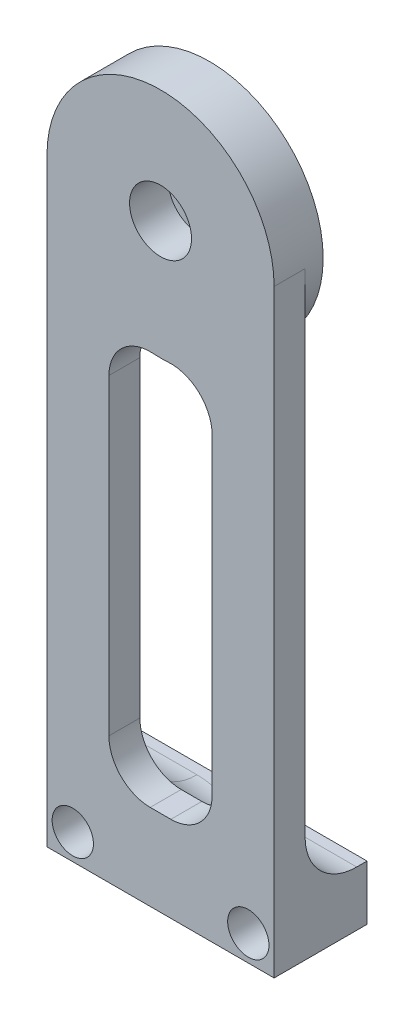
SolidWorks part; units mm, degrees
ref_plane "Front Plane" through (0, 0, 0) normal (0, 0, 1) x (1, 0, 0)
ref_plane "Top Plane" through (0, 0, 0) normal (0, 1, 0) x (1, 0, 0)
ref_plane "Right Plane" through (0, 0, 0) normal (1, 0, 0) x (0, 0, -1)
sketch "Sketch1" plane through (0, 0, 0) normal (0, 0, 1) x (1, 0, 0)
  line L0 (0, 29) -> (0, -29) construction
  line L1 (-11, 29) -> (-11, -29)
  line L2 (11, 29) -> (11, -29)
  line L3 (-11, -29) -> (11, -29)
  line L5 (-11, -29) -> (11, -29)
  line L6 (-11, -29) -> (-11, -23.69)
  line L7 (-11, -23.69) -> (11, -23.69)
  line L8 (11, -29) -> (11, -23.69)
  line L10 (-5, 18.6438) -> (-5, -20.69)
  line L11 (-5, -20.69) -> (5, -20.69)
  line L12 (5, 18.6438) -> (5, -20.69)
  circle A0 centre (0, 29) radius 11
  arc A2 (-5, 18.6438) -> (5, 18.6438) centre (0, 29) ccw
  point P8 (0, 0)
  dimension "D2" = 22
  dimension "D6" = 6
  dimension "D7" = 11.5
  dimension "D1" = 58
  dimension "D3" = 5.31
  dimension "D4" = 3
  dimension "D5" = 6
extrude "Boss-Extrude1" add sketch "Sketch1" along normal blind 3 contours A0 | L0 A0 L1 | A0 L0 L2 | L6 L5 L8 L7 region at (0, 17.9429, 0) region at (0, 29, 0)
extrude "Boss-Extrude2" add sketch "Sketch1<3>" against normal blind 1.75 contours A0 region at (0, 29, 0)
sketch "Sketch1<3>" plane through (0, 0, 0) normal (0, 0, 1) x (1, 0, 0) same geometry as "Sketch1"
sketch "Sketch2" plane through (0, 0, 3) normal (0, 0, 1) x (1, 0, 0)
  circle A0 centre (0, 29) radius 1.75
  circle A3 centre (0, 29) radius 3
  dimension "D1" = 3.5
  dimension "D2" = 6
extrude "Cut-Extrude1" cut sketch "Sketch2" against normal up to surface (4.75 mm away) contours A0 region at (0, 29, 3) up to face at (11, 29, -1.75)
extrude "Cut-Extrude2" cut sketch "Sketch2<3>" against normal offset from surface (3.75 mm away) 1 contours A3 A0 region at (-2.9151, 29, 3) up to face at (1.75, 29, -1.75)
sketch "Sketch2<3>" plane through (0, 0, 3) normal (0, 0, 1) x (1, 0, 0) same geometry as "Sketch2"
extrude "Boss-Extrude3" add sketch "Sketch1<6>" against normal blind 6 contours L7 L0 L5 L2 | L0 L7 L1 L3 region at (-5.5, -26.345, 0) region at (5.5, -26.345, 0)
sketch "Sketch1<6>" plane through (0, 0, 0) normal (0, 0, 1) x (1, 0, 0) same geometry as "Sketch1"
sketch "Sketch3" plane through (0, 0, 3) normal (0, 0, 1) x (1, 0, 0)
  line L1 (-8.5, -26.505) -> (8.5, -26.505) construction
  line L2 (-11, -29) -> (11, -29) construction
  circle A1 centre (-8.5, -26.505) radius 1.1
  circle A2 centre (8.5, -26.505) radius 1.1
  circle A3 centre (-8.5, -26.505) radius 2
  circle A4 centre (8.5, -26.505) radius 2
  point P5 (0, -26.505)
  dimension "D2" = 2.2
  dimension "D3" = 4
  dimension "D4" = 2.495
  dimension "D1" = 17
extrude "Cut-Extrude3" cut sketch "Sketch3" against normal up to surface (9 mm away) contours A1 | A2 region at (-8.5, -26.505, 3) up to face at (0, -26.345, -6)
extrude "Cut-Extrude4" cut sketch "Sketch3<3>" against normal offset from surface (8 mm away) 1 up to face at (-7.4, -26.505, -6)
sketch "Sketch3<3>" plane through (0, 0, 3) normal (0, 0, 1) x (1, 0, 0) same geometry as "Sketch3"
fillet "Filete1" radius 4 4 edges at (5, 18.6438, 1.5) (-5, 18.6438, 1.5) (5, -20.69, 1.5) (-5, -20.69, 1.5)
fillet "Filete2" radius 5 1 edges at (0, -23.69, 0)
move or copy body "Corpo-Mover/Copiar1" [suppressed] bodies to move or copy 118
